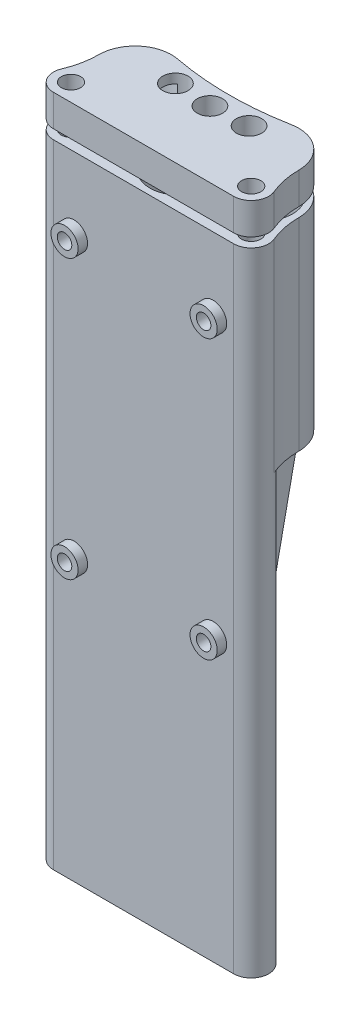
SolidWorks part; units mm, degrees
ref_plane "Front Plane" through (0, 0, 0) normal (0, 0, 1) x (1, 0, 0)
ref_plane "Top Plane" through (0, 0, 0) normal (0, 1, 0) x (1, 0, 0)
ref_plane "Right Plane" through (0, 0, 0) normal (1, 0, 0) x (0, 0, -1)
sketch "Sketch1" plane through (0, 0, 0) normal (0, 1, 0) x (1, 0, 0)
  line L0 (-28.5, 0) -> (28.5, 0) construction
  line L1 (-28.5, 0) -> (28.5, 0) construction
  line L2 (-28.5, 5.55) -> (28.5, 5.55)
  line L3 (-28.5, -5.55) -> (28.5, -5.55)
  circle A0 centre (-28.5, 0) radius 3.05
  circle A1 centre (28.5, 0) radius 3.05
  arc A2 (-28.5, 5.55) -> (-28.5, -5.55) centre (-28.5, 0) ccw
  arc A3 (28.5, -5.55) -> (28.5, 5.55) centre (28.5, 0) ccw
  point P4 (0, 0)
  dimension "D1" = 6.1
  dimension "D2" = 2.5
  dimension "D3" = 57
extrude "Boss-Extrude1" add sketch "Sketch1" along normal mid plane 200
sketch "Sketch2" plane through (0, 0, 0) normal (1, 0, 0) x (0, 0, -1)
  line L0 (5.55, 36.6649) -> (5.55, -0.5321)
  line L1 (5.55, 100) -> (5.55, -100) construction
  line L2 (5.55, -0.5321) -> (7.05, -0.5321)
  line L3 (7.05, -0.5321) -> (14.8208, 36.6649)
  line L4 (14.8208, 36.6649) -> (5.55, 36.6649)
  dimension "D1" = 11.8
  dimension "D2" = 38
  dimension "D3" = 1.5
extrude "Boss-Extrude2" add sketch "Sketch2" along normal up to vertex (28.5 mm away) and the other way up to vertex (28.5 mm away) up to point (28.5, 100, -5.55) other way up to point (-28.5, 100, -5.55)
sketch "Sketch3" plane through (0, -1.4335, -6.8617) normal (0, -0.2045, -0.9789) x (-1, 0, 0)
  line L0 (-14, 33.9209) -> (14, 5.9209) construction
  line L1 (0, 11.204) -> (0, -11.204) construction
  line L3 (-28.5, 0.9209) -> (-28.5, 38.9209) construction
  circle A0 centre (-14, 33.9209) radius 1.5
  circle A1 centre (-14, 5.9209) radius 1.5
  circle A2 centre (14, 33.9209) radius 1.5
  circle A3 centre (14, 5.9209) radius 1.5
  circle A4 centre (-14, 33.9209) radius 2.5
  circle A5 centre (14, 33.9209) radius 2.5
  circle A6 centre (14, 5.9209) radius 2.5
  circle A7 centre (-14, 5.9209) radius 2.5
  point P8 (0, 19.9209)
  point P13 (-28.5, 19.9209)
  dimension "D1" = 3
  dimension "D2" = 28
  dimension "D3" = 28
  dimension "D4" = 1
extrude "Boss-Extrude3" add sketch "Sketch3" along normal blind 1.5
chamfer "Chamfer1" distance 0.5 angle 45 4 edges at (14, 6.5027, -10.052) (-14, 6.5027, -10.052) (-14, 33.911, -15.7779) (14, 33.911, -15.7779)
sketch "Sketch6" plane through (0, 100, 0) normal (0, 1, 0) x (1, 0, 0)
  line L0 (-28.5, -5.55) -> (28.5, -5.55) construction
  line L3 (0, -17.5762) -> (0, 17.5762) construction
  line L4 (-28.5, -5.55) -> (28.5, -5.55)
  arc A0 (-3.9104, 14.6079) -> (3.9104, 14.6079) centre (0, 5.95) ccw
  arc A1 (-14.1587, 19.2894) -> (-10.6457, 12.3022) centre (-20.1375, 11.9067) ccw
  arc A2 (10.6457, 12.3022) -> (14.1587, 19.2894) centre (20.1375, 11.9067) ccw
  circle A4 centre (0, 5.95) radius 11.5 construction
  circle A6 centre (-20.1375, 11.9067) radius 11.5 construction
  circle A7 centre (20.1375, 11.9067) radius 11.5 construction
  circle A8 centre (-28.5, 0) radius 3.05 construction
  circle A10 centre (28.5, 0) radius 3.05 construction
  arc A11 (-31.6375, 11.9067) -> (-33.6123, 2.1604) centre (-56.6757, 11.9067) cw
  arc A12 (-28.5, 5.55) -> (-28.5, -5.55) centre (-28.5, 0) ccw construction
  arc A13 (-31.6375, 11.9067) -> (-17.9882, 23.2041) centre (-20.1375, 11.9067) cw
  arc A14 (31.6375, 11.9067) -> (17.9882, 23.2041) centre (20.1375, 11.9067) ccw
  arc A15 (31.6375, 11.9067) -> (33.6123, 2.1604) centre (56.6757, 11.9067) ccw
  arc A16 (28.5, -5.55) -> (28.5, 5.55) centre (28.5, 0) ccw construction
  arc A17 (-17.9882, 23.2041) -> (17.9882, 23.2041) centre (0, 117.7561) ccw
  arc A18 (-10.6457, 12.3022) -> (-14.1587, 19.2894) centre (-11.6498, 16.1741) ccw
  arc A19 (3.9104, 14.6079) -> (-3.9104, 14.6079) centre (0, 15.45) ccw
  arc A20 (14.1587, 19.2894) -> (10.6457, 12.3022) centre (11.6498, 16.1741) ccw
  circle A21 centre (-11.6498, 16.1741) radius 6 construction
  circle A22 centre (-11.6498, 16.1741) radius 4 construction
  circle A23 centre (-20.1375, 11.9067) radius 9.5 construction
  circle A24 centre (0, 5.95) radius 9.5 construction
  circle A25 centre (20.1375, 11.9067) radius 9.5 construction
  arc A26 (-33.6123, 2.1604) -> (-28.5, -5.55) centre (-28.5, 0) ccw
  arc A27 (33.6123, 2.1604) -> (28.5, -5.55) centre (28.5, 0) cw
  circle A28 centre (-28.5, 0) radius 3.05
  circle A29 centre (28.5, 0) radius 3.05
  line M6 (28.5, 5.55) -> (-28.5, 5.55)
  dimension "D1" = 19
  dimension "D4" = 8
  dimension "D2" = 2
  dimension "D3" = 2
  dimension "D5" = 2
extrude "Boss-Extrude5" add sketch "Sketch6" against normal blind 60
extrude "Cut-Extrude2" cut sketch "Sketch6<2>" against normal up to surface (60 mm away) contours A1 M6 | A0 M6 | A2 M6 region at (20.1375, 100, -4.273) region at (-20.1375, 100, -4.273) region at (0, 100, -1.7011) up to face at (0, 40, -11.9943)
sketch "Sketch6<2>" plane through (0, 100, 0) normal (0, 1, 0) x (1, 0, 0) same geometry as "Sketch6"
sketch "Sketch7" plane through (0, 40, 0) normal (0, -1, 0) x (1, 0, 0)
  line L0 (-28.5, -5.55) -> (28.5, -5.55)
  line L4 (-9.4916, -5.55) -> (-13.0776, -5.55)
  line L5 (-27.1973, -5.55) -> (-28.5, -5.55)
  line L6 (28.5, -5.55) -> (27.1973, -5.55)
  line L7 (13.0776, -5.55) -> (9.4916, -5.55)
  arc A16 (-10.6457, -12.3022) -> (-13.0776, -5.55) centre (-20.1375, -11.9067) ccw
  arc A17 (-14.1587, -19.2894) -> (-10.6457, -12.3022) centre (-11.6498, -16.1741) ccw
  arc A18 (-27.1973, -5.55) -> (-14.1587, -19.2894) centre (-20.1375, -11.9067) ccw
  arc A20 (-31.6375, -11.9067) -> (-33.6123, -2.1604) centre (-56.6757, -11.9067) ccw
  arc A21 (-31.6375, -11.9067) -> (-17.9882, -23.2041) centre (-20.1375, -11.9067) ccw
  arc A22 (17.9882, -23.2041) -> (-17.9882, -23.2041) centre (0, -117.7561) ccw
  arc A23 (17.9882, -23.2041) -> (31.6375, -11.9067) centre (20.1375, -11.9067) ccw
  arc A24 (33.6123, -2.1604) -> (31.6375, -11.9067) centre (56.6757, -11.9067) ccw
  arc A26 (14.1587, -19.2894) -> (27.1973, -5.55) centre (20.1375, -11.9067) ccw
  arc A27 (10.6457, -12.3022) -> (14.1587, -19.2894) centre (11.6498, -16.1741) ccw
  arc A28 (13.0776, -5.55) -> (10.6457, -12.3022) centre (20.1375, -11.9067) ccw
  arc A29 (3.9104, -14.6079) -> (9.4916, -5.55) centre (0, -5.95) ccw
  arc A30 (-3.9104, -14.6079) -> (3.9104, -14.6079) centre (0, -15.45) ccw
  arc A31 (-9.4916, -5.55) -> (-3.9104, -14.6079) centre (0, -5.95) ccw
  arc A36 (-31.6375, -11.9067) -> (-33.6123, -2.1604) centre (-56.6757, -11.9067) ccw
  arc A37 (-31.6375, -11.9067) -> (-17.9882, -23.2041) centre (-20.1375, -11.9067) ccw
  arc A38 (17.9882, -23.2041) -> (-17.9882, -23.2041) centre (0, -117.7561) ccw
  arc A39 (17.9882, -23.2041) -> (31.6375, -11.9067) centre (20.1375, -11.9067) ccw
  arc A40 (33.6123, -2.1604) -> (31.6375, -11.9067) centre (56.6757, -11.9067) ccw
  arc A48 (-33.6123, -2.1604) -> (-28.5, -5.55) centre (-28.5, 0) ccw
  arc A49 (-33.6123, -2.1604) -> (-28.5, -5.55) centre (-28.5, 0) ccw
  arc A50 (28.5, -5.55) -> (33.6123, -2.1604) centre (28.5, 0) ccw
  arc A51 (28.5, -5.55) -> (33.6123, -2.1604) centre (28.5, 0) ccw
  dimension "D1" = 0
extrude "Boss-Extrude6" add sketch "Sketch7" along normal blind 4
extrude "Boss-Extrude7" add sketch "Sketch6<3>" along normal blind 7 from offset 3 separate body
sketch "Sketch6<3>" plane through (0, 100, 0) normal (0, 1, 0) x (1, 0, 0) same geometry as "Sketch6"
sketch "Sketch9" plane through (0, 110, 0) normal (0, 1, 0) x (1, 0, 0)
  line L1 (-28.5, -5.55) -> (28.5, -5.55)
  line L2 (-28.5, -5.55) -> (28.5, -5.55)
  circle A0 centre (-11.6498, 16.1741) radius 4
  circle A1 centre (0, 15.45) radius 4
  circle A2 centre (11.6498, 16.1741) radius 4
  arc A3 (14.1587, 19.2894) -> (10.6457, 12.3022) centre (11.6498, 16.1741) ccw construction
  arc A4 (3.9104, 14.6079) -> (-3.9104, 14.6079) centre (0, 15.45) ccw construction
  arc A5 (-10.6457, 12.3022) -> (-14.1587, 19.2894) centre (-11.6498, 16.1741) ccw construction
  circle A6 centre (28.5, 0) radius 3.05 construction
  arc A7 (-17.9882, 23.2041) -> (-31.6375, 11.9067) centre (-20.1375, 11.9067) ccw
  arc A8 (-33.6123, 2.1604) -> (-31.6375, 11.9067) centre (-56.6757, 11.9067) ccw
  arc A9 (-33.6123, 2.1604) -> (-28.5, -5.55) centre (-28.5, 0) ccw
  arc A10 (28.5, -5.55) -> (33.6123, 2.1604) centre (28.5, 0) ccw
  arc A11 (31.6375, 11.9067) -> (33.6123, 2.1604) centre (56.6757, 11.9067) ccw
  arc A12 (31.6375, 11.9067) -> (17.9882, 23.2041) centre (20.1375, 11.9067) ccw
  arc A13 (-17.9882, 23.2041) -> (17.9882, 23.2041) centre (0, 117.7561) ccw
  arc A14 (-17.9882, 23.2041) -> (-31.6375, 11.9067) centre (-20.1375, 11.9067) ccw
  arc A15 (-33.6123, 2.1604) -> (-31.6375, 11.9067) centre (-56.6757, 11.9067) ccw
  arc A16 (-33.6123, 2.1604) -> (-28.5, -5.55) centre (-28.5, 0) ccw
  arc A17 (28.5, -5.55) -> (33.6123, 2.1604) centre (28.5, 0) ccw
  arc A18 (31.6375, 11.9067) -> (33.6123, 2.1604) centre (56.6757, 11.9067) ccw
  arc A19 (31.6375, 11.9067) -> (17.9882, 23.2041) centre (20.1375, 11.9067) ccw
  arc A20 (-17.9882, 23.2041) -> (17.9882, 23.2041) centre (0, 117.7561) ccw
  circle A21 centre (-28.5, 0) radius 3.05 construction
  circle A22 centre (28.5, 0) radius 3.05
  circle A23 centre (-28.5, 0) radius 3.05
  dimension "D1" = 0
extrude "Boss-Extrude8" add sketch "Sketch9" along normal blind 3
sketch "Sketch4" plane through (0, 0, 5.55) normal (0, 0, 1) x (1, 0, 0)
  line L0 (0, -17.5762) -> (0, 17.5762) construction
  line L1 (-26, 100) -> (26, 100) construction
  line L2 (-26, 100) -> (-26, -15) construction
  line L3 (-26, -15) -> (26, -15) construction
  line L4 (26, 100) -> (26, -15) construction
  line L5 (-28.5, 100) -> (28.5, 100) construction
  line L6 (-22, 77) -> (22, 77) construction
  line L7 (-22, -11) -> (22, -11) construction
  circle A0 centre (-22, 77) radius 2.3
  circle A1 centre (22, 77) radius 2.3
  circle A2 centre (-22, -11) radius 2.3
  circle A3 centre (22, -11) radius 2.3
  circle A4 centre (-22, 77) radius 4.3
  circle A5 centre (22, 77) radius 4.3
  circle A6 centre (-22, -11) radius 4.3
  circle A7 centre (22, -11) radius 4.3
  point P4 (0, 100)
  point P12 (0, 77)
  point P16 (0, -11)
  dimension "D7" = 4.6
  dimension "D1" = 52
  dimension "D2" = 115
  dimension "D3" = 23
  dimension "D4" = 4
  dimension "D5" = 4
  dimension "D6" = 4
  dimension "D8" = 2
extrude "Boss-Extrude4" add sketch "Sketch4" along normal blind 3
extrude "Cut-Extrude1" cut sketch "Sketch4<2>" against normal blind 3 contours A1 | A0 | A3 | A2 region at (-22, 77, 5.55) region at (22, 77, 5.55) region at (-22, -11, 5.55) region at (22, -11, 5.55)
sketch "Sketch4<2>" plane through (0, 0, 5.55) normal (0, 0, 1) x (1, 0, 0) same geometry as "Sketch4"
sketch "Sketch10" plane through (0, 0, -5.55) normal (0, 0, -1) x (-1, 0, 0)
  line L0 (0, 17.5762) -> (0, -17.5762) construction
  line L1 (-24.5, -5.5321) -> (24.5, -5.5321) construction
  line L2 (-24.5, -5.5321) -> (-24.5, -63.5321) construction
  line L3 (-24.5, -63.5321) -> (24.5, -63.5321) construction
  line L4 (24.5, -5.5321) -> (24.5, -63.5321) construction
  line L5 (-28.5, -0.5321) -> (28.5, -0.5321) construction
  line L7 (-22.9123, -2.7821) -> (-26.0877, -2.7821)
  line L8 (-26.0877, -2.7821) -> (-27.6754, -5.5321)
  line L9 (-27.6754, -5.5321) -> (-26.0877, -8.2821)
  line L10 (-26.0877, -8.2821) -> (-22.9123, -8.2821)
  line L11 (-22.9123, -8.2821) -> (-21.3246, -5.5321)
  line L12 (-21.3246, -5.5321) -> (-22.9123, -2.7821)
  line L13 (26.0877, -2.7821) -> (22.9123, -2.7821)
  line L14 (22.9123, -2.7821) -> (21.3246, -5.5321)
  line L15 (21.3246, -5.5321) -> (22.9123, -8.2821)
  line L16 (22.9123, -8.2821) -> (26.0877, -8.2821)
  line L17 (26.0877, -8.2821) -> (27.6754, -5.5321)
  line L18 (27.6754, -5.5321) -> (26.0877, -2.7821)
  line L19 (-22.9123, -60.7821) -> (-26.0877, -60.7821)
  line L20 (-26.0877, -60.7821) -> (-27.6754, -63.5321)
  line L21 (-27.6754, -63.5321) -> (-26.0877, -66.2821)
  line L22 (-26.0877, -66.2821) -> (-22.9123, -66.2821)
  line L23 (-22.9123, -66.2821) -> (-21.3246, -63.5321)
  line L24 (-21.3246, -63.5321) -> (-22.9123, -60.7821)
  line L25 (22.9123, -60.7821) -> (21.3246, -63.5321)
  line L26 (21.3246, -63.5321) -> (22.9123, -66.2821)
  line L27 (22.9123, -66.2821) -> (26.0877, -66.2821)
  line L28 (26.0877, -66.2821) -> (27.6754, -63.5321)
  line L29 (27.6754, -63.5321) -> (26.0877, -60.7821)
  line L30 (26.0877, -60.7821) -> (22.9123, -60.7821)
  circle A0 centre (-24.5, -5.5321) radius 1.5
  circle A1 centre (24.5, -5.5321) radius 1.5
  circle A2 centre (24.5, -63.5321) radius 1.5
  circle A3 centre (-24.5, -63.5321) radius 1.5
  circle A4 centre (-24.5, -5.5321) radius 2.75 construction
  circle A5 centre (24.5, -5.5321) radius 2.75 construction
  circle A6 centre (-24.5, -63.5321) radius 2.75 construction
  circle A7 centre (24.5, -63.5321) radius 2.75 construction
  point P8 (0, -5.5321)
  dimension "D1" = 3
  dimension "D2" = 49
  dimension "D3" = 58
  dimension "D4" = 5
  dimension "D5" = 5.5
extrude "Cut-Extrude3" cut sketch "Sketch10" against normal blind 2
extrude "Cut-Extrude4" cut sketch "Sketch10<3>" against normal blind 8 contours A0 | A1 | A3 | A2 region at (24.5, -5.5321, -5.55) region at (-24.5, -5.5321, -5.55) region at (-24.5, -63.5321, -5.55) region at (24.5, -63.5321, -5.55)
sketch "Sketch10<3>" plane through (0, 0, -5.55) normal (0, 0, -1) x (-1, 0, 0) same geometry as "Sketch10"
